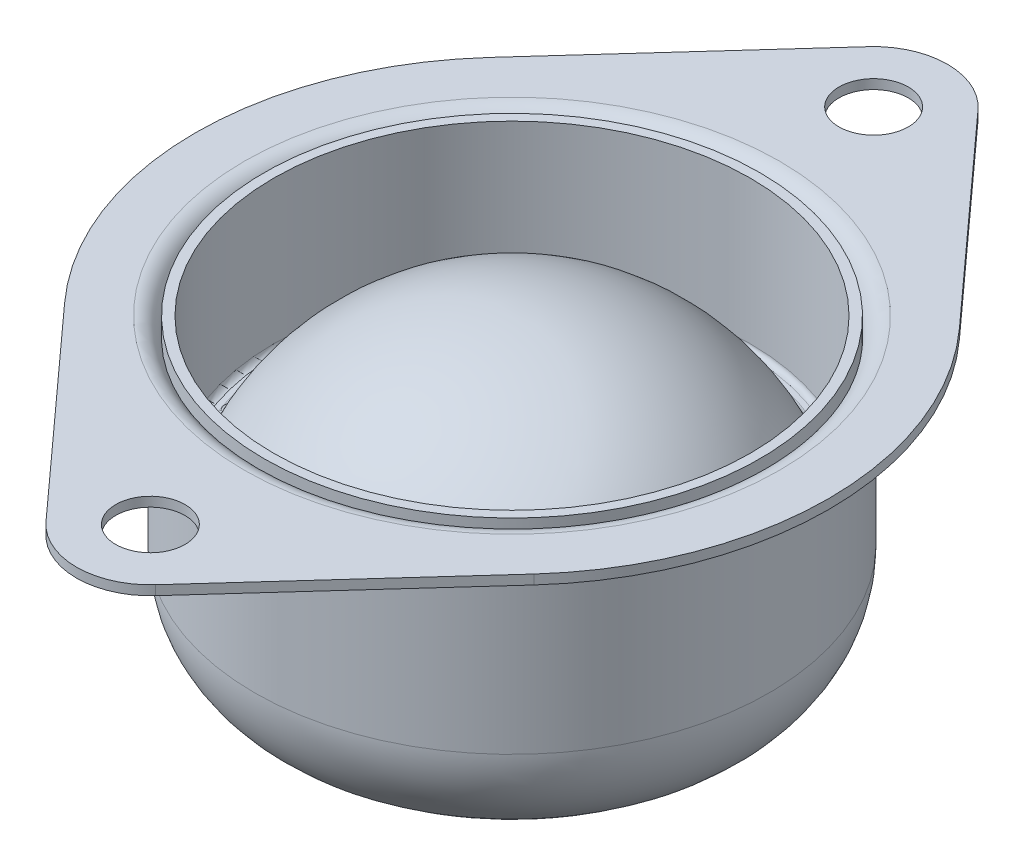
SolidWorks part; units mm, degrees
ref_plane "Front" through (0, 0, 0) normal (0, 0, 1) x (1, 0, 0)
ref_plane "Top" through (0, 0, 0) normal (0, 1, 0) x (1, 0, 0)
ref_plane "Right" through (0, 0, 0) normal (1, 0, 0) x (0, 0, -1)
sketch "Sketch1" plane through (0, 0, 0) normal (0, 1, 0) x (1, 0, 0)
  line L0 (0, -29) -> (0, 29) construction
  line L1 (18.8203, -17.0574) -> (4.3902, -32.9789)
  line L2 (-4.3902, -32.9789) -> (-18.8203, -17.0574)
  line L3 (-4.3902, 32.9789) -> (-18.8203, 17.0574)
  line L4 (18.8203, 17.0574) -> (4.3902, 32.9789)
  circle A0 centre (0, 0) radius 20.6375 construction
  arc A1 (18.8203, -17.0574) -> (18.8203, 17.0574) centre (0, 0) ccw
  arc A2 (4.3902, 32.9789) -> (-4.3902, 32.9789) centre (0, 29) ccw
  arc A3 (-4.3902, -32.9789) -> (4.3902, -32.9789) centre (0, -29) ccw
  arc A4 (-18.8203, 17.0574) -> (-18.8203, -17.0574) centre (0, 0) ccw
  circle A5 centre (0, 29) radius 2.7781
  circle A6 centre (0, -29) radius 2.7781
  point P5 (0, 0)
  dimension "D1" = 41.275
  dimension "D3" = 50.8
  dimension "D4" = 69.85
  dimension "D5" = 5.5562
  dimension "D2" = 58
extrude "Boss-Extrude1" add sketch "Sketch1" along normal blind 0.762
ref_axis "Axis1" through (0, -30.9086, 0) along (0, 1, 0)
sketch "Sketch2" plane through (0, 0, 0) normal (0, -1, 0) x (1, 0, 0)
  circle A0 centre (0, 0) radius 20.6375 construction
  circle A1 centre (0, 0) radius 20.6375
extrude "Boss-Extrude2" add sketch "Sketch2" along normal offset from surface (23.8442 mm away) 24.6062 up to face at (0, 0.762, -26.2219)
fillet "Fillet1" radius 8.7312 1 edges at (0, -23.8442, 20.6375)
shell "Shell1" thickness 0.762 removed face at (0, 0.762, -26.2219)
fillet "Fillet2" radius 1.5875 2 edges at (0, 0, 20.6375) (0, 0.762, 19.8755)
sketch "Sketch6" plane through (0, -23.8443, 0) normal (0, -1, 0) x (1, 0, 0)
  circle A1 centre (0, 0) radius 11.9062
  circle A2 centre (0, 0) radius 11.9062
  dimension "D1" = 0
extrude "Cut-Extrude3" cut sketch "Sketch6" against normal up to surface (0.762 mm away) up to face at (0, -23.0822, 11.9062)
sketch "Sketch7" plane through (0, 0.762, 0) normal (0, 1, 0) x (1, 0, 0)
  circle A0 centre (0, 0) radius 19.8755 construction
  circle A1 centre (0, 0) radius 19.8755
extrude "Boss-Extrude3" add sketch "Sketch7" against normal blind 12.7 separate body
sketch "Sketch8" plane through (0, 0, 0) normal (1, 0, 0) x (0, 0, -1)
  line L0 (-19.8755, -11.938) -> (19.8755, -11.938) construction
  line L1 (0, 0) -> (0, -11.938)
  line L2 (0, -11.938) -> (-17.4625, -11.938)
  arc A0 (-17.4625, -11.938) -> (0, 0) centre (0, -18.7408) cw
  arc A1 (0, 0) -> (17.4625, -11.938) centre (0, -18.7408) cw construction
  dimension "D1" = 34.925
revolve "Cut-Revolve1" cut sketch "Sketch8" angle 360 about axis through (0, -30.9086, 0) along (0, 1, 0)
fillet "Fillet3" radius 1.1906 2 edges at (0, -11.938, 19.8755) (0, -11.938, -17.4625)
shell "Shell2" thickness 0.762 removed face at (0, 0.762, 19.8755)
sketch "Sketch3" plane through (0, 0, 0) normal (1, 0, 0) x (0, 0, -1)
  line L0 (17.0574, 0.762) -> (-17.0574, 0.762) construction
  line L1 (0, -29.4005) -> (0, -4.0005)
  arc A0 (0, -4.0005) -> (0, -29.4005) centre (0, -16.7005) ccw
  point P8 (0, -16.7005)
  dimension "D1" = 25.4
  dimension "D2" = 30.1625
revolve "Revolve1" add sketch "Sketch3" angle 360 about axis through (0, -106.8222, 0) along (0, 1, 0)
